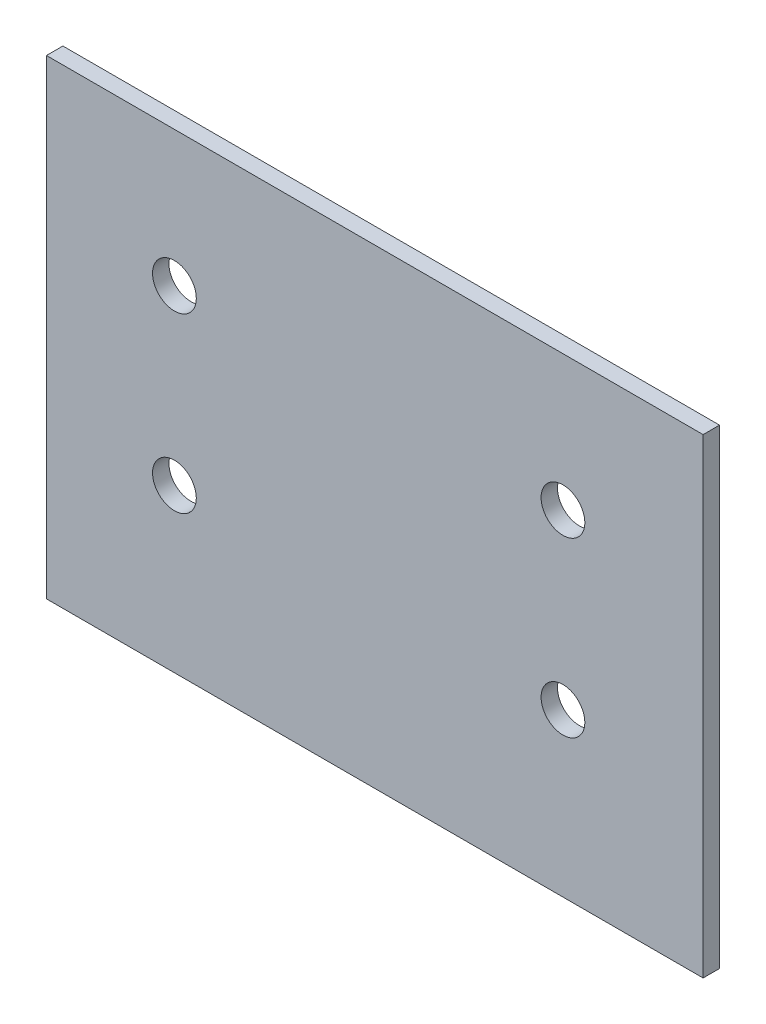
SolidWorks part; units mm, degrees
ref_plane "Front Plane" through (0, 0, 0) normal (0, 0, 1) x (1, 0, 0)
ref_plane "Top Plane" through (0, 0, 0) normal (0, 1, 0) x (1, 0, 0)
ref_plane "Right Plane" through (0, 0, 0) normal (1, 0, 0) x (0, 0, -1)
sketch "Sketch1" plane through (0, 0, 0) normal (0, 0, 1) x (1, 0, 0)
  line L1 (-38.1, 27.305) -> (38.1, 27.305)
  line L2 (-38.1, 27.305) -> (-38.1, -27.305)
  line L3 (-38.1, -27.305) -> (38.1, -27.305)
  line L4 (38.1, 27.305) -> (38.1, -27.305)
  line L5 (-38.1, 27.305) -> (38.1, -27.305) construction
  line L6 (-38.1, -27.305) -> (38.1, 27.305) construction
  point P0 (0, 0)
  dimension "D13" = 76.2
  dimension "D2" = 54.61
extrude "Boss-Extrude1" add sketch "Sketch1" along normal blind 1.905
sketch "Sketch2" plane through (0, 0, 1.905) normal (0, 0, 1) x (1, 0, 0)
  circle A0 centre (-23.2525, 11.584) radius 2.54
  circle A1 centre (-23.2525, -8.482) radius 2.54
  circle A2 centre (21.8341, 11.584) radius 2.54
  circle A3 centre (21.8341, -8.482) radius 2.54
  dimension "D1" = 5.08
  dimension "D2" = 20.066
extrude "Cut-Extrude1" cut sketch "Sketch2" against normal through all
